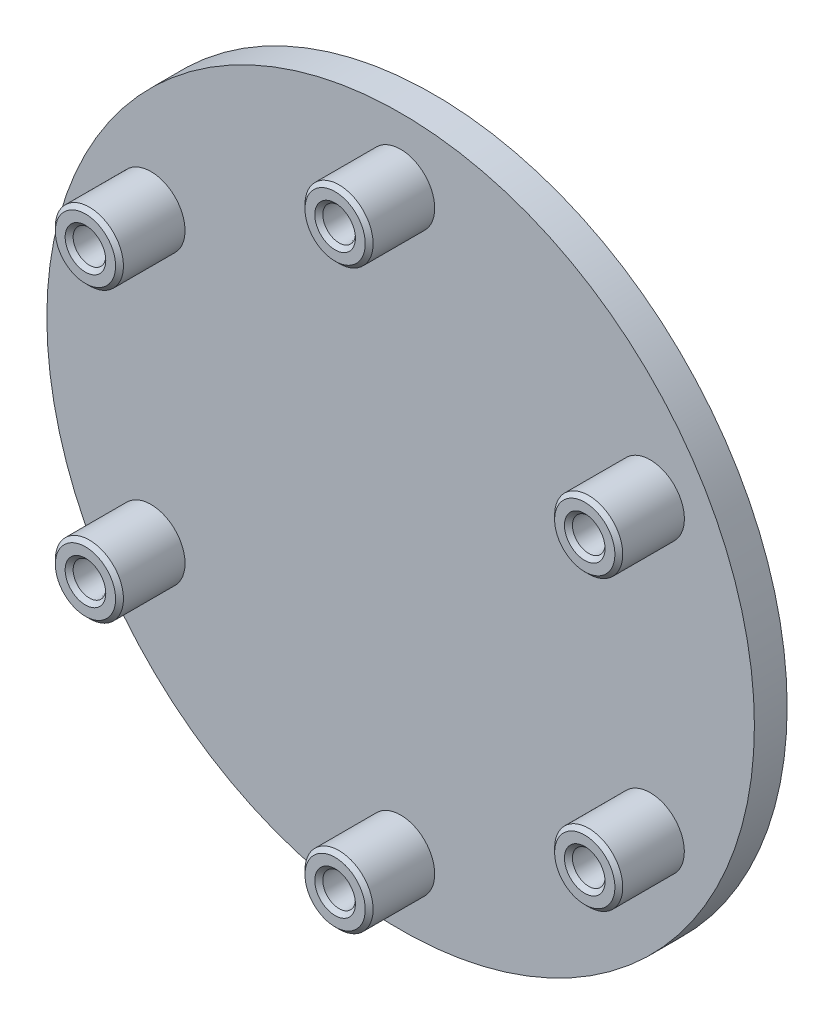
SolidWorks part; units mm, degrees
ref_plane "Front Plane" through (0, 0, 0) normal (0, 0, 1) x (1, 0, 0)
ref_plane "Top Plane" through (0, 0, 0) normal (0, 1, 0) x (1, 0, 0)
ref_plane "Right Plane" through (0, 0, 0) normal (1, 0, 0) x (0, 0, -1)
sketch "Sketch1" plane through (0, 0, 0) normal (0, 0, 1) x (1, 0, 0)
  circle A0 centre (0, 0) radius 34.29
  dimension "D1" = 68.58
extrude "Boss-Extrude1" add sketch "Sketch1" along normal blind 3.175
ref_axis "Axis1" through (0, 0, -0.1588) along (0, 0, 1)
sketch "Sketch2" plane through (0, 0, 3.175) normal (0, 0, 1) x (1, 0, 0)
  line L0 (0, 0) -> (0, 27.94) construction
  circle A1 centre (0, 27.94) radius 3.302
  dimension "D1" = 6.604
  dimension "D2" = 27.94
extrude "Boss-Extrude2" add sketch "Sketch2" along normal blind 6.35
sketch "Sketch3" plane through (0, 0, 9.525) normal (0, 0, 1) x (1, 0, 0)
  circle A0 centre (0, 27.94) radius 1.5875
  dimension "D1" = 3.175
extrude "Cut-Extrude1" cut sketch "Sketch3" against normal blind 4.572 draft 1
chamfer "Chamfer1" distance 0.381 angle 45 2 edges at (1.5875, 27.94, 9.525) (3.302, 27.94, 9.525) first distance on face at (1.5875, 27.94, 9.525) first distance on face at (3.302, 27.94, 9.525)
pattern_circular "CirPattern1" count 6 over 360 about axis through (0, 0, -0.1588) along (0, 0, 1) of "Boss-Extrude2", "Chamfer1", "Cut-Extrude1"
sketch "Sketch4" plane through (0, 0, 3.175) normal (0, 0, 1) x (1, 0, 0)
  circle A0 centre (0, 27.94) radius 6.35
  circle A1 centre (0, 27.94) radius 66.3924
extrude "Cut-Extrude2" [suppressed] cut sketch "Sketch4" against normal through all both and the other way through all
sketch "Sketch5" [suppressed] plane through (0, 0, 0) normal (0, 1, 0) x (1, 0, 0)
  line L1 (6.35, 0) -> (-6.35, 0)
  line L2 (6.35, 0) -> (6.35, -3.175)
  line L3 (6.35, -3.175) -> (-6.35, -3.175)
  line L4 (-6.35, 0) -> (-6.35, -3.175)
extrude "Cut-Extrude3" [suppressed] cut sketch "Sketch5" against normal through all both and the other way through all
